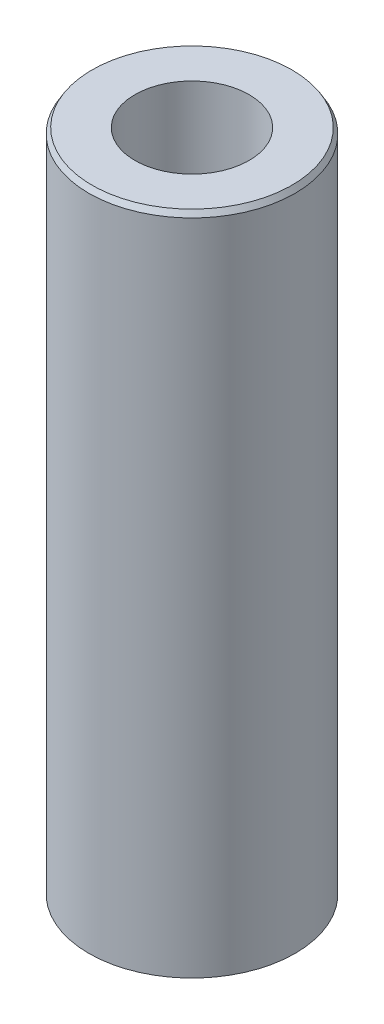
SolidWorks part; units mm, degrees
ref_plane "Front Plane" through (0, 0, 0) normal (0, 0, 1) x (1, 0, 0)
ref_plane "Top Plane" through (0, 0, 0) normal (0, 1, 0) x (1, 0, 0)
ref_plane "Right Plane" through (0, 0, 0) normal (1, 0, 0) x (0, 0, -1)
sketch "Sketch1" plane through (0, 0, 0) normal (0, 1, 0) x (1, 0, 0)
  circle A0 centre (0, 0) radius 60
  dimension "SHAFT_OD" = 120
extrude "Boss-Extrude1" add sketch "Sketch1" along normal blind 387.839
sketch "Sketch2" plane through (0, 0, 0) normal (0, 1, 0) x (1, 0, 0)
  circle A0 centre (0, 0) radius 33.2
  dimension "BORE_D" = 66.3999
extrude "Cut-Extrude1" cut sketch "Sketch2" along normal through all
chamfer "Chamfer1" distance 3.1262 angle 30.939 2 edges at (0, 387.839, 60) (0, 0, 60) first distance on face at (0, 387.839, 60) first distance on face at (0, 0, 33.2)
